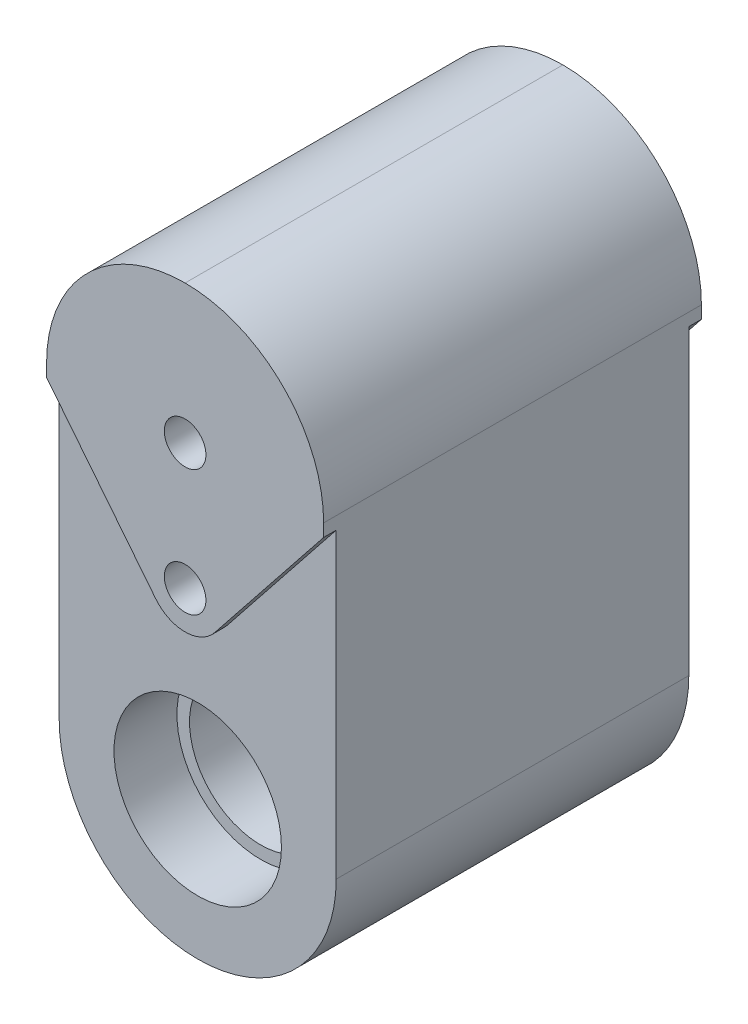
SolidWorks part; units mm, degrees
ref_plane "Спереди" through (0, 0, 0) normal (0, 0, 1) x (1, 0, 0)
ref_plane "Сверху" through (0, 0, 0) normal (0, 1, 0) x (1, 0, 0)
ref_plane "Справа" through (0, 0, 0) normal (1, 0, 0) x (0, 0, -1)
sketch "Эскиз1" plane through (0, 0, 0) normal (0, 0, 1) x (1, 0, 0)
  line L0 (0, 36) -> (0, -11) construction
  line L1 (-11, 36) -> (11, 36)
  line L2 (-11, 36) -> (-11, -11)
  line L3 (-11, -11) -> (11, -11)
  line L4 (11, 36) -> (11, -11)
  line L6 (-11, 0) -> (11, 0) construction
  dimension "D1" = 22
  dimension "D2" = 11
  dimension "D3" = 36
extrude "тело" add sketch "Эскиз1" along normal blind 14 and the other way blind 14
sketch "Эскиз2" plane through (0, 0, 14) normal (0, 0, 1) x (1, 0, 0)
  circle A0 centre (0, 0) radius 6.65
  dimension "D1" = 13.3
extrude "углубление для подшипника" cut sketch "Эскиз2" against normal blind 5
sketch "Эскиз4" plane through (0, 0, 9) normal (0, 0, 1) x (1, 0, 0)
  line L1 (0, 36) -> (0, -11) construction
  line L2 (-11, 0) -> (11, 0) construction
  circle A0 centre (0, 0) radius 5.65
  circle A1 centre (0, 0) radius 6.65 construction
  dimension "D1" = 1
extrude "сквозное отверстие" cut sketch "Эскиз4" against normal through all
mirror "Зеркальное отражение2" about plane through (0, 0, 0) normal (0, 0, 1) of "углубление для подшипника"
sketch "Эскиз5" plane through (0, 0, -14) normal (0, 0, -1) x (-1, 0, 0)
  line L0 (0, 36) -> (0, -11) construction
  line L1 (-11, 36) -> (11, 36) construction
  line L2 (11, -11) -> (-11, -11) construction
  circle A0 centre (0, 25) radius 1.65
  circle A1 centre (0, 15) radius 1.65
  circle A2 centre (0, 0) radius 6.65 construction
  dimension "D1" = 3.3
  dimension "D2" = 10
  dimension "D3" = 15
extrude "отверстия под болты" cut sketch "Эскиз5" against normal through all
sketch "Эскиз9" plane through (0, 0, 14) normal (0, 0, 1) x (1, 0, 0)
  line L0 (-11, 36) -> (-11, 24)
  line L1 (-11, 36) -> (-11, -11) construction
  line L2 (-11, 36) -> (11, 36)
  line L3 (-11, 24) -> (-2.347, 13.1314)
  line L4 (11, 36) -> (11, 24)
  line L5 (11, 24) -> (2.347, 13.1314)
  line L6 (11, -11) -> (11, 36) construction
  arc A0 (-2.347, 13.1314) -> (2.347, 13.1314) centre (0, 15) ccw
  circle A1 centre (0, 15) radius 1.65
  circle A2 centre (0, 25) radius 1.65
  circle A3 centre (0, 25) radius 1.65 construction
  circle A4 centre (0, 15) radius 1.65 construction
  dimension "D1" = 6
  dimension "D2" = 12
extrude "выступы" add sketch "Эскиз9" along normal blind 1
mirror "Зеркальное отражение1" about plane through (0, 0, 0) normal (0, 0, 1) of "выступы"
fillet "Скругление1" radius 11 4 edges at (11, -11, 0) (-11, -11, 0) (-11, 36, 0) (11, 36, 0)
